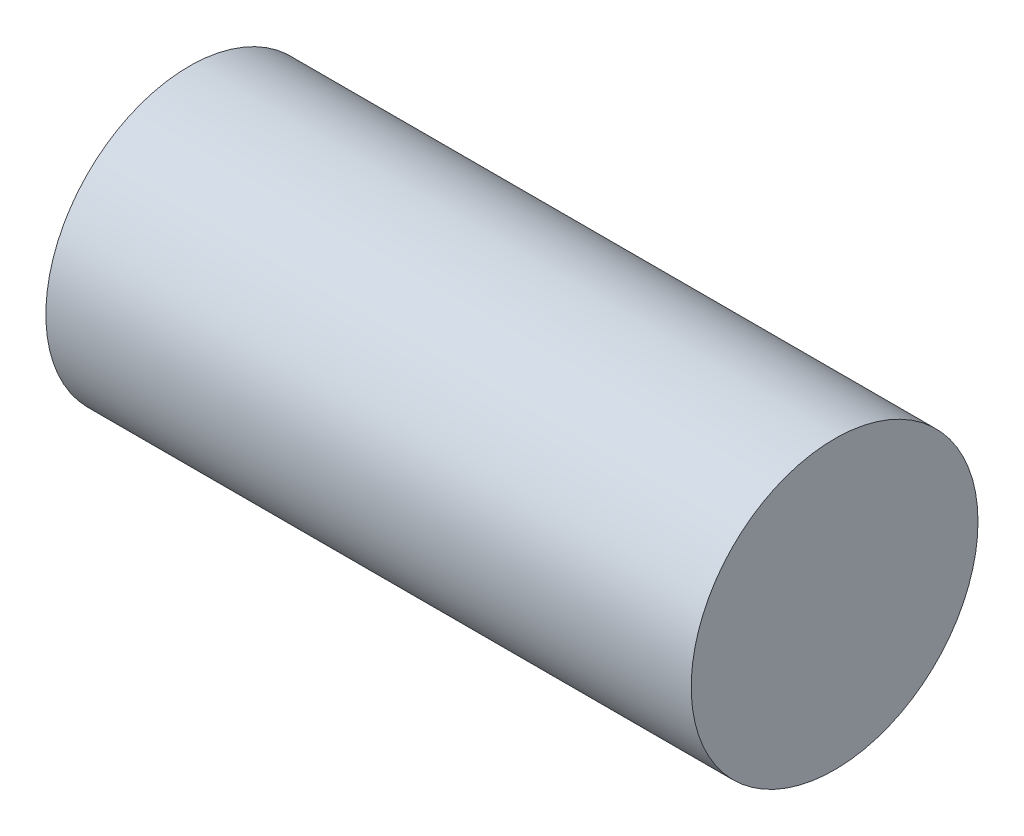
SolidWorks part; units mm, degrees
material "1.5714 (16NiCr4)"
ref_plane "Front Plane" through (0, 0, 0) normal (0, 0, 1) x (1, 0, 0)
ref_plane "Top Plane" through (0, 0, 0) normal (0, 1, 0) x (1, 0, 0)
ref_plane "Right Plane" through (0, 0, 0) normal (1, 0, 0) x (0, 0, -1)
sketch "Schizzo1" plane through (0, 0, 0) normal (1, 0, 0) x (0, 0, -1)
  circle A0 centre (0, 0) radius 4
  dimension "D1" = 8
extrude "Estrusione-Estrusione1" add sketch "Schizzo1" along normal blind 18
